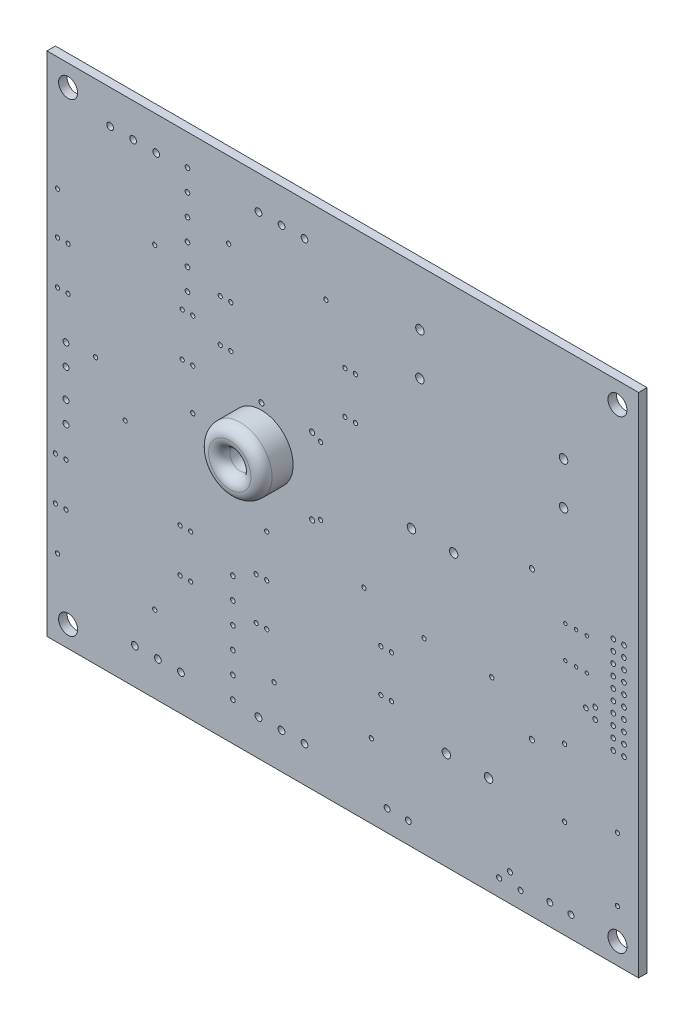
SolidWorks part; units mm, degrees
ref_plane "Спереди" through (0, 0, 0) normal (0, 0, 1) x (1, 0, 0)
ref_plane "Сверху" through (0, 0, 0) normal (0, 1, 0) x (1, 0, 0)
ref_plane "Справа" through (0, 0, 0) normal (1, 0, 0) x (0, 0, -1)
sketch "Эскиз1" plane through (0, 0, 0) normal (0, 0, 1) x (1, 0, 0)
  line L0 (-22.6071, 0) -> (23.7373, 0) construction
  line L1 (-70, -60) -> (70, -60)
  line L2 (-70, -60) -> (-70, 60)
  line L3 (-70, 60) -> (70, 60)
  line L4 (70, -60) -> (70, 60)
  line L5 (0, 0) -> (0, 31.6453) construction
  circle A0 centre (-65, -55) radius 2.25
  circle A1 centre (65, -55) radius 2.25
  circle A2 centre (65, 55) radius 2.25
  circle A3 centre (-65, 55) radius 2.25
  dimension "D3" = 4.5
  dimension "D1" = 140
  dimension "D2" = 120
  dimension "D4" = 5
  dimension "D5" = 5
extrude "Вытянуть1" add sketch "Эскиз1" along normal blind 2
sketch "Эскиз2" plane through (0, 0, 2) normal (0, 0, 1) x (1, 0, 0)
  line L0 (-70, 60) -> (-70, -60) construction
  line L1 (-70, -60) -> (70, -60) construction
  line L2 (-19.95, 52) -> (-9.05, 52) construction
  line L3 (-19.95, -51.5) -> (-9.05, -51.5) construction
  line L4 (64, 6.5) -> (66.54, 6.5) construction
  line L14 (65, -47.75) -> (65, -32.75) construction
  line L15 (-55.05, 52) -> (-44.15, 52) construction
  line L16 (-49.2, -51.5) -> (-38.3, -51.5) construction
  line L17 (-36.75, 27.3) -> (-36.75, 47.62) construction
  line L18 (-36.75, 47.62) -> (-36.75, 52.7) construction
  line L19 (19.25, -15.75) -> (35.25, -15.75) construction
  line L20 (-5.25, -3.75) -> (-5.25, 12.25) construction
  circle A0 centre (64, 6.5) radius 0.55
  circle A1 centre (66.54, 6.5) radius 0.55
  circle A2 centre (64, 3.96) radius 0.55
  circle A3 centre (66.54, 3.96) radius 0.55
  circle A4 centre (64, 1.42) radius 0.55
  circle A5 centre (66.54, 1.42) radius 0.55
  circle A6 centre (64, -1.12) radius 0.55
  circle A7 centre (66.54, -1.12) radius 0.55
  circle A8 centre (64, -3.66) radius 0.55
  circle A9 centre (66.54, -3.66) radius 0.55
  circle A10 centre (64, -6.2) radius 0.55
  circle A11 centre (66.54, -6.2) radius 0.55
  circle A12 centre (64, -8.74) radius 0.55
  circle A13 centre (66.54, -8.74) radius 0.55
  circle A14 centre (64, -11.28) radius 0.55
  circle A15 centre (66.54, -11.28) radius 0.55
  circle A16 centre (64, -13.82) radius 0.55
  circle A17 centre (66.54, -13.82) radius 0.55
  circle A18 centre (64, -16.36) radius 0.55
  circle A19 centre (66.54, -16.36) radius 0.55
  circle A20 centre (65, -47.75) radius 0.5
  circle A21 centre (65, -32.75) radius 0.5
  circle A22 centre (-55.05, 52) radius 0.8
  circle A23 centre (-49.6, 52) radius 0.8
  circle A24 centre (-44.15, 52) radius 0.8
  circle A25 centre (-19.95, 52) radius 0.8
  circle A26 centre (-14.5, 52) radius 0.8
  circle A27 centre (-9.05, 52) radius 0.8
  circle A28 centre (-49.2, -51.5) radius 0.8
  circle A29 centre (-43.75, -51.5) radius 0.8
  circle A30 centre (-38.3, -51.5) radius 0.8
  circle A31 centre (-19.95, -51.5) radius 0.8
  circle A32 centre (-14.5, -51.5) radius 0.8
  circle A33 centre (-9.05, -51.5) radius 0.8
  circle A34 centre (-26, -50.95) radius 0.55
  circle A35 centre (-26, -45.87) radius 0.55
  circle A36 centre (-26, -40.79) radius 0.55
  circle A37 centre (-26, -35.71) radius 0.55
  circle A38 centre (-26, -30.63) radius 0.55
  circle A39 centre (-26, -25.55) radius 0.55
  circle A40 centre (-36.75, 27.3) radius 0.55
  circle A41 centre (-36.75, 32.38) radius 0.55
  circle A42 centre (-36.75, 37.46) radius 0.55
  circle A43 centre (-36.75, 42.54) radius 0.55
  circle A44 centre (-36.75, 47.62) radius 0.55
  circle A45 centre (-36.75, 52.7) radius 0.55
  circle A46 centre (19.25, -15.75) radius 0.5
  circle A47 centre (35.25, -15.75) radius 0.5
  circle A48 centre (-5.25, -3.75) radius 0.5
  circle A49 centre (-5.25, 12.25) radius 0.5
  dimension "D3" = 1.1
  dimension "D4" = 2.54
  dimension "D7" = 1
  dimension "D8" = 135
  dimension "D9" = 1.6
  dimension "D10" = 10.9
  dimension "D11" = 14.95
  dimension "D12" = 112
  dimension "D13" = 1.6
  dimension "D19" = 5.45
  dimension "D20" = 5.45
  dimension "D23" = 1.1
  dimension "D14" = 10.9
  dimension "D26" = 5.08
  dimension "D27" = 5.08
  dimension "D28" = 5.08
  dimension "D29" = 5.08
  dimension "D30" = 5.08
  dimension "D32" = 112.7
  dimension "D6" = 15
  dimension "D33" = 16
  dimension "D34" = 1
  dimension "D36" = 89.25
  dimension "D37" = 1
  dimension "D1" = 134
  dimension "D2" = 66.5
  dimension "D5" = 12.25
  dimension "D15" = 50.05
  dimension "D16" = 112
  dimension "D17" = 8.5
  dimension "D18" = 8.5
  dimension "D21" = 20.8
  dimension "D22" = 50.05
  dimension "D24" = 9.05
  dimension "D25" = 44
  dimension "D31" = 33.25
  dimension "D35" = 44.25
  dimension "D38" = 16
  dimension "D39" = 64.75
  dimension "D40" = 72.25
extrude "Вырез-Вытянуть1" cut sketch "Эскиз2" against normal blind 2
sketch "Эскиз3" plane through (0, 0, 2) normal (0, 0, 1) x (1, 0, 0)
  line L0 (-70, -60) -> (70, -60) construction
  line L1 (-70, 60) -> (-70, -60) construction
  line L2 (57.75, 4) -> (57.75, -3.62) construction
  line L3 (59.73, -10.875) -> (56.2465, -10.875) construction
  line L4 (59.73, -9.605) -> (59.73, -15.0734) construction
  line L5 (49, -55) -> (54, -55) construction
  line L6 (10.5, -55) -> (15.5, -55) construction
  line L7 (-65.5, -2.5) -> (-65.5, 2.5) construction
  line L8 (-65.5, -14.25) -> (-65.5, -9.25) construction
  line L11 (37, -56) -> (42.08, -56) construction
  line L12 (52.5, -36.75) -> (52.5, -20.75) construction
  line L13 (44.75, -23.75) -> (44.75, 11.25) construction
  line L14 (52.25, 27.5) -> (52.25, 37.5) construction
  line L15 (18.25, 37) -> (18.25, 47) construction
  line L16 (16.25, 5.25) -> (26.25, 5.25) construction
  line L17 (24.5, -36.75) -> (34.5, -36.75) construction
  circle A0 centre (57.75, 4) radius 0.4
  circle A1 centre (57.75, -3.62) radius 0.4
  circle A2 centre (55.21, -3.62) radius 0.4
  circle A3 centre (55.21, 4) radius 0.4
  circle A4 centre (52.67, -3.62) radius 0.4
  circle A5 centre (52.67, 4) radius 0.4
  circle A6 centre (59.73, -9.605) radius 0.55
  circle A7 centre (59.73, -12.145) radius 0.55
  circle A8 centre (57.54, -10.875) radius 0.55
  circle A9 centre (49, -55) radius 0.7
  circle A10 centre (10.5, -55) radius 0.7
  circle A11 centre (54, -55) radius 0.7
  circle A12 centre (15.5, -55) radius 0.7
  circle A13 centre (-65.5, -2.5) radius 0.7
  circle A14 centre (-65.5, 2.5) radius 0.7
  circle A15 centre (-65.5, -14.25) radius 0.7
  circle A16 centre (-65.5, -9.25) radius 0.7
  circle A17 centre (37, -56) radius 0.6
  circle A18 centre (42.08, -56) radius 0.6
  circle A19 centre (39.54, -53.46) radius 0.6
  circle A20 centre (52.5, -36.75) radius 0.5
  circle A21 centre (52.5, -20.75) radius 0.5
  circle A22 centre (44.75, -23.75) radius 0.6
  circle A23 centre (44.75, 11.25) radius 0.6
  circle A24 centre (52.25, 27.5) radius 1
  circle A25 centre (52.25, 37.5) radius 1
  circle A26 centre (18.25, 37) radius 1
  circle A27 centre (18.25, 47) radius 1
  circle A28 centre (16.25, 5.25) radius 1
  circle A29 centre (26.25, 5.25) radius 1
  circle A30 centre (24.5, -36.75) radius 1
  circle A31 centre (34.5, -36.75) radius 1
  dimension "D1" = 0.8
  dimension "D4" = 7.62
  dimension "D5" = 1.1
  dimension "D8" = 2.54
  dimension "D9" = 127.54
  dimension "D10" = 119
  dimension "D11" = 5
  dimension "D16" = 80.5
  dimension "D17" = 5
  dimension "D18" = 62.5
  dimension "D22" = 1.2
  dimension "D23" = 5.08
  dimension "D24" = 2.54
  dimension "D25" = 2.54
  dimension "D28" = 1
  dimension "D32" = 1.2
  dimension "D36" = 10
  dimension "D37" = 2
  dimension "D41" = 2
  dimension "D43" = 97
  dimension "D44" = 10
  dimension "D14" = 5
  dimension "D15" = 5
  dimension "D13" = 1.4
  dimension "D30" = 16
  dimension "D35" = 35
  dimension "D20" = 1.4
  dimension "D50" = 1.4
  dimension "D2" = 64
  dimension "D3" = 127.75
  dimension "D6" = 50.395
  dimension "D7" = 129.73
  dimension "D12" = 5
  dimension "D19" = 4.5
  dimension "D21" = 5
  dimension "D26" = 4
  dimension "D27" = 107
  dimension "D29" = 23.25
  dimension "D31" = 122.5
  dimension "D33" = 114.75
  dimension "D34" = 36.25
  dimension "D38" = 122.25
  dimension "D39" = 87.5
  dimension "D40" = 10
  dimension "D42" = 88.25
  dimension "D45" = 65.25
  dimension "D46" = 86.25
  dimension "D47" = 10
  dimension "D48" = 23.25
  dimension "D49" = 94.5
  dimension "D51" = 4.5
  dimension "D52" = 50.75
extrude "Вырез-Вытянуть2" cut sketch "Эскиз3" against normal blind 10
sketch "Эскиз4" plane through (0, 0, 2) normal (0, 0, 1) x (1, 0, 0)
  line L0 (-19.25, -4.75) -> (-19.25, 13.25) construction
  line L1 (-70, 60) -> (-70, -60) construction
  line L2 (-70, -60) -> (70, -60) construction
  line L3 (-7.25, 13.25) -> (-7.25, -4.75) construction
  line L4 (-67.5, -41.75) -> (-44.5, -41.75) construction
  line L5 (-67.5, 33) -> (-44.5, 33) construction
  line L6 (-68, -31.75) -> (-36, -31.75) construction
  line L7 (-68, -21.5) -> (-36, -21.5) construction
  line L8 (-51.5, -6.5) -> (-28.5, -6.5) construction
  line L9 (-58.5, 3) -> (-35.5, 3) construction
  line L10 (-67.5, 12.75) -> (-35.5, 12.75) construction
  line L11 (-67.5, 23) -> (-35.5, 23) construction
  line L12 (-29, 20.25) -> (3, 20.25) construction
  line L13 (-29, 30.25) -> (3, 30.25) construction
  line L14 (-27, 42) -> (-4, 42) construction
  line L15 (-16.25, -42.5) -> (6.75, -42.5) construction
  line L16 (-20.5, -32.5) -> (11.5, -32.5) construction
  line L17 (-20.5, -22.5) -> (11.5, -22.5) construction
  line L18 (-18, -12.5) -> (5, -12.5) construction
  circle A0 centre (-19.25, -4.75) radius 0.6
  circle A1 centre (-19.25, 2.75) radius 0.6
  circle A2 centre (-19.25, 5.75) radius 0.6
  circle A3 centre (-19.25, 13.25) radius 0.6
  circle A4 centre (-7.25, 13.25) radius 0.6
  circle A5 centre (-7.25, -4.75) radius 0.6
  circle A6 centre (-67.5, -41.75) radius 0.5
  circle A7 centre (-44.5, -41.75) radius 0.5
  circle A8 centre (-67.5, 33) radius 0.5
  circle A9 centre (-44.5, 33) radius 0.5
  circle A10 centre (-68, -31.75) radius 0.5
  circle A11 centre (-36, -31.75) radius 0.5
  circle A12 centre (-65.5, -31.75) radius 0.5
  circle A13 centre (-38.5, -31.75) radius 0.5
  circle A14 centre (-68, -21.5) radius 0.5
  circle A15 centre (-36, -21.5) radius 0.5
  circle A16 centre (-65.5, -21.5) radius 0.5
  circle A17 centre (-38.5, -21.5) radius 0.5
  circle A18 centre (-51.5, -6.5) radius 0.5
  circle A19 centre (-28.5, -6.5) radius 0.5
  circle A20 centre (-58.5, 3) radius 0.5
  circle A21 centre (-35.5, 3) radius 0.5
  circle A22 centre (-67.5, 12.75) radius 0.5
  circle A23 centre (-35.5, 12.75) radius 0.5
  circle A24 centre (-65, 12.75) radius 0.5
  circle A25 centre (-38, 12.75) radius 0.5
  circle A26 centre (-67.5, 23) radius 0.5
  circle A27 centre (-35.5, 23) radius 0.5
  circle A28 centre (-65, 23) radius 0.5
  circle A29 centre (-38, 23) radius 0.5
  circle A30 centre (-29, 20.25) radius 0.5
  circle A31 centre (3, 20.25) radius 0.5
  circle A32 centre (-26.5, 20.25) radius 0.5
  circle A33 centre (0.5, 20.25) radius 0.5
  circle A34 centre (-29, 30.25) radius 0.5
  circle A35 centre (3, 30.25) radius 0.5
  circle A36 centre (-26.5, 30.25) radius 0.5
  circle A37 centre (0.5, 30.25) radius 0.5
  circle A38 centre (-27, 42) radius 0.5
  circle A39 centre (-4, 42) radius 0.5
  circle A40 centre (-16.25, -42.5) radius 0.5
  circle A41 centre (6.75, -42.5) radius 0.5
  circle A42 centre (-20.5, -32.5) radius 0.5
  circle A43 centre (11.5, -32.5) radius 0.5
  circle A44 centre (-18, -32.5) radius 0.5
  circle A45 centre (9, -32.5) radius 0.5
  circle A46 centre (-20.5, -22.5) radius 0.5
  circle A47 centre (11.5, -22.5) radius 0.5
  circle A48 centre (-18, -22.5) radius 0.5
  circle A49 centre (9, -22.5) radius 0.5
  circle A50 centre (-18, -12.5) radius 0.5
  circle A51 centre (5, -12.5) radius 0.5
  dimension "D5" = 73.25
  dimension "D6" = 1.2
  dimension "D9" = 73.25
  dimension "D10" = 23
  dimension "D12" = 1
  dimension "D15" = 1
  dimension "D19" = 2.5
  dimension "D24" = 27
  dimension "D25" = 32
  dimension "D26" = 2.5
  dimension "D29" = 1
  dimension "D31" = 1
  dimension "D37" = 32
  dimension "D38" = 32
  dimension "D39" = 2.5
  dimension "D40" = 2.5
  dimension "D41" = 27
  dimension "D42" = 27
  dimension "D52" = 1
  dimension "D55" = 1
  dimension "D56" = 41
  dimension "D57" = 32
  dimension "D58" = 27
  dimension "D59" = 2.5
  dimension "D60" = 32
  dimension "D62" = 1
  dimension "D64" = 1
  dimension "D66" = 53.75
  dimension "D70" = 52
  dimension "D71" = 27
  dimension "D72" = 32
  dimension "D73" = 2.5
  dimension "D74" = 49.5
  dimension "D75" = 32
  dimension "D76" = 27
  dimension "D77" = 2.5
  dimension "D78" = 49.5
  dimension "D1" = 50.75
  dimension "D2" = 55.25
  dimension "D3" = 62.75
  dimension "D4" = 65.75
  dimension "D7" = 62.75
  dimension "D8" = 55.25
  dimension "D11" = 2.5
  dimension "D13" = 18.25
  dimension "D14" = 23
  dimension "D16" = 93
  dimension "D17" = 2.5
  dimension "D18" = 2
  dimension "D20" = 31.5
  dimension "D21" = 34
  dimension "D22" = 28.25
  dimension "D23" = 38.5
  dimension "D27" = 2
  dimension "D28" = 23
  dimension "D30" = 23
  dimension "D32" = 53.5
  dimension "D33" = 63
  dimension "D34" = 18.5
  dimension "D35" = 11.5
  dimension "D36" = 10.25
  dimension "D43" = 2.5
  dimension "D44" = 72.75
  dimension "D45" = 2.5
  dimension "D46" = 10
  dimension "D47" = 2.5
  dimension "D48" = 27
  dimension "D49" = 41
  dimension "D50" = 80.25
  dimension "D51" = 23
  dimension "D53" = 43
  dimension "D54" = 102
  dimension "D61" = 23
  dimension "D63" = 23
  dimension "D65" = 17.5
  dimension "D67" = 27.5
  dimension "D68" = 10
  dimension "D69" = 47.5
extrude "Вырез-Вытянуть3" cut sketch "Эскиз4" against normal blind 10
sketch "Эскиз5" plane through (0, 0, 2) normal (0, 0, 1) x (1, 0, 0)
  line L0 (-19.25, 2.75) -> (-19.25, 5.75) construction
  line L1 (-21.2798, 4.25) -> (-17.2511, 4.25) construction
  circle A0 centre (-19.25, 4.25) radius 2.5
  circle A1 centre (-19.25, 4.25) radius 7.5
  circle A2 centre (-19.25, 5.75) radius 0.6 construction
  circle A3 centre (-19.25, 2.75) radius 0.6 construction
  dimension "D1" = 5
  dimension "D2" = 15
extrude "Вытянуть2" add sketch "Эскиз5" along normal blind 7.5
fillet "Скругление1" radius 2.5 2 edges at (-16.75, 4.25, 9.5) (-11.75, 4.25, 9.5)
